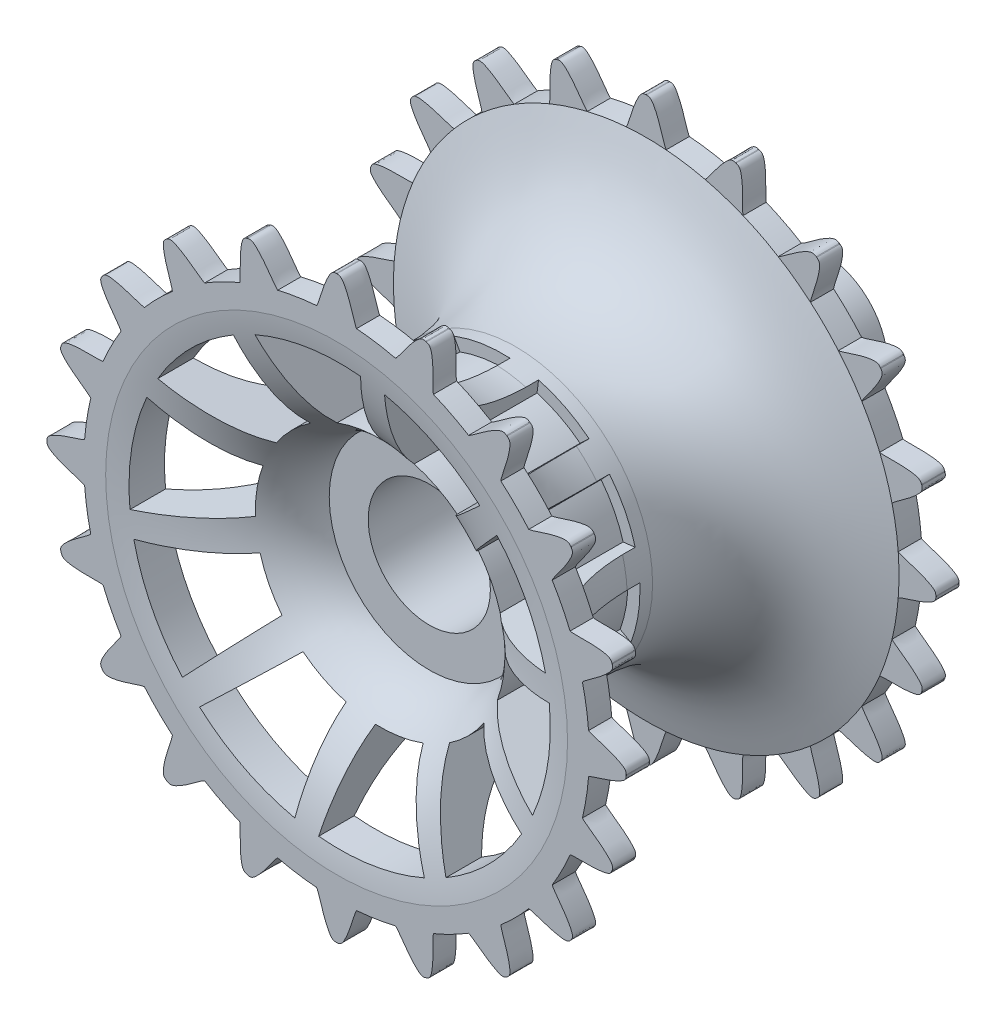
SolidWorks part; units mm, degrees
ref_plane "前视基准面" through (0, 0, 0) normal (0, 0, 1) x (1, 0, 0)
ref_plane "上视基准面" through (0, 0, 0) normal (0, 1, 0) x (1, 0, 0)
ref_plane "右视基准面" through (0, 0, 0) normal (1, 0, 0) x (0, 0, -1)
sketch "草图1" plane through (0, 0, 0) normal (0, 0, 1) x (1, 0, 0)
  line L0 (0, 0) -> (0, 27.5)
  line L1 (0, 0) -> (4.0987, 27.1928)
  line L2 (0, 0) -> (8.1058, 26.2783)
  line L3 (0, 0) -> (11.9318, 24.7766)
  line L4 (0, 0) -> (15.4913, 22.7216)
  line L5 (0, 0) -> (18.7048, 20.1589)
  line L6 (0, 0) -> (21.5004, 17.146)
  line L7 (0, 0) -> (23.8157, 13.75)
  line L8 (0, 0) -> (25.599, 10.0469)
  line L9 (0, 0) -> (26.8105, 6.1193)
  line L10 (0, 0) -> (27.4231, 2.0551)
  line L11 (0, 0) -> (27.4231, -2.0551)
  line L12 (0, 0) -> (26.8105, -6.1193)
  line L13 (0, 0) -> (25.599, -10.0469)
  line L14 (0, 0) -> (23.8157, -13.75)
  line L15 (0, 0) -> (21.5004, -17.146)
  line L16 (0, 0) -> (18.7048, -20.1589)
  line L17 (0, 0) -> (15.4913, -22.7216)
  line L18 (0, 0) -> (11.9318, -24.7766)
  line L19 (0, 0) -> (8.1058, -26.2783)
  line L20 (0, 0) -> (4.0987, -27.1928)
  line L21 (0, 0) -> (0, -27.5)
  line L22 (0, 0) -> (-4.0987, -27.1928)
  line L23 (0, 0) -> (-8.1058, -26.2783)
  line L24 (0, 0) -> (-11.9318, -24.7766)
  line L25 (0, 0) -> (-15.4913, -22.7216)
  line L26 (0, 0) -> (-18.7048, -20.1589)
  line L27 (0, 0) -> (-21.5004, -17.146)
  line L28 (0, 0) -> (-23.8157, -13.75)
  line L29 (0, 0) -> (-25.599, -10.0469)
  line L30 (0, 0) -> (-26.8105, -6.1193)
  line L31 (0, 0) -> (-27.4231, -2.0551)
  line L32 (0, 0) -> (-27.4231, 2.0551)
  line L33 (0, 0) -> (-26.8105, 6.1193)
  line L34 (0, 0) -> (-25.599, 10.0469)
  line L35 (0, 0) -> (-23.8157, 13.75)
  line L36 (0, 0) -> (-21.5004, 17.146)
  line L37 (0, 0) -> (-18.7048, 20.1589)
  line L38 (-13.5197, 19.8297) -> (-15.4913, 22.7216)
  line L39 (0, 0) -> (-11.9318, 24.7766)
  line L40 (0, 0) -> (-8.1058, 26.2783)
  line L41 (0, 0) -> (-4.0987, 27.1928)
  circle A0 centre (0, 0) radius 27.5
  circle A1 centre (0, 0) radius 24
  arc A2 (-7.5899, 24.606) -> (3.8378, 25.4624) centre (0, 0) ccw
  arc A3 (0, 25.75) -> (-3.8378, 25.4624) centre (0, 0) ccw
  spline S0 degree 3 poles (0, 27.5) (0.1146, 27.5014) (0.3487, 27.4756) (0.6091, 27.1808) (0.8232, 26.7995) (1.0497, 26.2917) (1.3089, 25.6127) (1.5804, 24.8085) (1.748, 24.1915) (1.8927, 23.9253) knots 0 0 0 0 0.082079 0.155052 0.267882 0.395303 0.549244 0.784807 1 1 1 1
  spline S1 degree 3 poles (0, 27.5) (-0.1146, 27.5014) (-0.3487, 27.4756) (-0.6091, 27.1808) (-0.8232, 26.7995) (-1.0497, 26.2917) (-1.3089, 25.6127) (-1.5804, 24.8085) (-1.748, 24.1915) (-1.8927, 23.9253) knots 0 0 0 0 0.082079 0.155052 0.267882 0.395303 0.549244 0.784807 1 1 1 1
  point P7 (-14.5055, 21.2756)
  point P48 (0, 0)
  dimension "D1" = 42
extrude "凸台-拉伸1" add sketch "草图1" along normal blind 31.6 contours S0 A0 L0 A1 | A3 S1 A1 L0 | A0 S1 A3 L0 region at (-0.476, 26.4646, 0) region at (0.6795, 25.3953, 0) region at (-0.7923, 24.8026, 0)
sketch "草图2" plane through (0, 0, 31.6) normal (0, 0, 1) x (1, 0, 0)
  circle A0 centre (0, 0) radius 24
extrude "凸台-拉伸2" add sketch "草图2" against normal blind 31.6
ref_axis "基准轴1" through (0, 0, 0) along (0, 0, 1)
pattern_circular "阵列(圆周)1" count 20 over 360 about axis through (0, 0, 0) along (0, 0, 1) of "凸台-拉伸1"
ref_plane "基准面1" through (0, 0, 29.4) normal (0, 0, 1) x (1, 0, 0)
ref_plane "基准面2" through (0, 0, 2.2) normal (0, 0, -1) x (-1, 0, 0)
sketch "草图3" plane through (0, 0, 29.4) normal (0, 0, 1) x (1, 0, 0)
  circle A0 centre (0, 0) radius 24
  circle A1 centre (0, 0) radius 39.1983
extrude "切除-拉伸1" cut sketch "草图3" against normal up to surface (27.2 mm away) up to plane "基准面2"
sketch "草图4" plane through (0, 0, 0) normal (1, 0, 0) x (0, 0, -1)
  line L0 (-2.2, 24) -> (-29.4, 24) construction
  line L1 (-2.2, 24) -> (-29.4, 24)
  line L2 (-29.4, -24) -> (-2.2, -24) construction
  line L3 (-29.4, -24) -> (-2.2, -24)
  line L4 (-15.8, -24) -> (-15.8, 24)
  line L5 (-46.2378, 0) -> (16.3604, 0)
  line L6 (-46.2378, -13) -> (16.3604, -13)
  line L7 (-46.2378, 13) -> (16.3604, 13)
  spline S0 degree 3 poles (-29.4, 24) (-28.6064, 21.6025) (-27.2686, 17.3198) (-21.841, 13.3668) (-17.9343, 12.9408) (-15.8, 13) knots 0 0 0 0 0.401325 0.665617 1 1 1 1
  spline S1 degree 3 poles (-2.2, 24) (-2.9936, 21.6025) (-4.3314, 17.3198) (-9.759, 13.3668) (-13.6657, 12.9408) (-15.8, 13) knots 0 0 0 0 0.401325 0.665617 1 1 1 1
revolve "切除-旋转1" cut sketch "草图4" angle 360 about L5 region at (0, 19.2493, 10.1874) region at (0, 19.2493, 21.4126)
sketch "草图5" plane through (0, 0, 0) normal (1, 0, 0) x (0, 0, -1)
  line L0 (-31.6, 12.5317) -> (-31.6, 9.1934) construction
  line L1 (-17.0021, 13) -> (-17.0021, -13) construction
  line L2 (-31.6, 0) -> (-31.6, 9.5)
  line L3 (-17.0021, 13) -> (-17.0021, -13)
  line L4 (-14.5979, 13) -> (-14.5979, -13) construction
  line L5 (-14.5979, 13) -> (-14.5979, -13)
  line L6 (-17.0021, 13) -> (-14.5979, 13)
  line L7 (-15.8, 13) -> (-15.8, 0)
  line L8 (-15.8, 0) -> (-15.8, 9.5)
  line L9 (-15.8, 9.5) -> (-22.8, 9.5)
  line L10 (-22.8, 9.5) -> (-22.8, 0)
  line L11 (-22.8, 0) -> (-31.6, 0)
  line L12 (-31.6, 27.5) -> (-31.6, 23.9253) construction
  line L13 (-31.6, 27.5) -> (-31.6, 23.9253)
  line L14 (-31.6, 21.9281) -> (-31.6, 0)
  spline S1 degree 3 poles (-31.6, 21.9281) (-31.059, 16.9429) (-28.6782, 10.2775) (-22.8, 9.5) knots 0 0 0 0 1 1 1 1
revolve "切除-旋转2" cut sketch "草图5" angle 360 about axis through (0, 0, 0) along (0, 0, 1) region at (0, 6.7239, 27.7812)
ref_plane "基准面3" through (0, 0, 15.8) normal (0, 0, 1) x (1, 0, 0)
mirror "镜向1" about plane through (0, 0, 15.8) normal (0, 0, 1) of "切除-旋转2"
sketch "草图6" plane through (0, 0, 31.6) normal (0, 0, 1) x (1, 0, 0)
  line L0 (3.7544, 23.7045) -> (0, 0)
  line L1 (16.9706, 16.9706) -> (0, 0)
  line L2 (23.7045, 3.7544) -> (0, 0)
  line L3 (21.3842, -10.8958) -> (0, 0)
  line L4 (10.8958, -21.3842) -> (0, 0)
  line L5 (-3.7544, -23.7045) -> (0, 0)
  line L6 (-16.9706, -16.9706) -> (0, 0)
  line L7 (-23.7045, -3.7544) -> (0, 0)
  line L8 (-21.3842, 10.8958) -> (0, 0)
  line L9 (-10.8958, 21.3842) -> (0, 0)
  line L10 (3.2323, 11.4007) -> (4.2584, 19.5414)
  line L11 (7.3234, 9.3161) -> (13.3063, 14.9313)
  line L12 (0.4489, 11.8415) -> (1.9886, 19.9009)
  line L13 (9.3161, 7.3234) -> (14.9313, 13.3063)
  line L14 (11.4007, 3.2323) -> (19.5414, 4.2584)
  line L15 (11.8415, 0.4489) -> (19.9009, 1.9886)
  line L16 (11.1232, -4.0862) -> (18.3124, -8.041)
  line L17 (9.8438, -6.5971) -> (17.269, -10.0886)
  line L18 (6.5971, -9.8438) -> (10.0886, -17.269)
  line L19 (4.0862, -11.1232) -> (8.041, -18.3124)
  line L20 (-0.4489, -11.8415) -> (-1.9886, -19.9009)
  line L21 (-3.2323, -11.4007) -> (-4.2584, -19.5414)
  line L22 (-7.3234, -9.3161) -> (-13.3063, -14.9313)
  line L23 (-9.3161, -7.3234) -> (-14.9313, -13.3063)
  line L24 (-11.4007, -3.2323) -> (-19.5414, -4.2584)
  line L25 (-11.8415, -0.4489) -> (-19.9009, -1.9886)
  line L26 (-11.1232, 4.0862) -> (-18.3124, 8.041)
  line L27 (-9.8438, 6.5971) -> (-17.269, 10.0886)
  line L28 (-6.5971, 9.8438) -> (-10.0886, 17.269)
  line L29 (-4.0862, 11.1232) -> (-8.041, 18.3124)
  arc A0 (5.5932, 23.3391) -> (1.8927, 23.9253) centre (0, 0) ccw construction
  circle A1 centre (0, 0) radius 11.85
  circle A2 centre (0, 0) radius 20
  point P17 (0, 0)
  point P60 (0, 0)
  dimension "D2" = 10
  dimension "D1" = 10
extrude "切除-拉伸2" cut sketch "草图6" against normal up to surface (15.8 mm away) contours L12 A2 L29 A1 | L11 A2 L10 A1 | L14 A2 L13 A1 | L16 A2 L15 A1 | L18 A2 L17 A1 | L20 A2 L19 A1 | L22 A2 L21 A1 | L24 A2 L23 A1 | L26 A2 L25 A1 | L28 A2 L27 A1 region at (7.3935, 14.5105, 31.6) region at (-2.5476, 16.085, 31.6) region at (14.5105, 7.3935, 31.6) region at (16.085, -2.5476, 31.6) region at (11.5156, -11.5156, 31.6) region at (2.5476, -16.085, 31.6) region at (-7.3935, -14.5105, 31.6) region at (-14.5105, -7.3935, 31.6) region at (-16.085, 2.5476, 31.6) region at (-11.5156, 11.5156, 31.6) up to plane "基准面3"
sketch "草图7" plane through (0, 0, 22.8) normal (0, 0, 1) x (1, 0, 0)
  circle A0 centre (0, 0) radius 5.8
extrude "切除-拉伸3" cut sketch "草图7" against normal blind 13.5
sketch "草图8" plane through (0, 0, 9.3) normal (0, 0, 1) x (1, 0, 0)
  circle A0 centre (0, 0) radius 1.65
extrude "切除-拉伸4" cut sketch "草图8" against normal through all
sketch "草图9" plane through (0, 0, 8.8) normal (0, 0, -1) x (-1, 0, 0)
  circle A0 centre (0, 0) radius 1.65
  circle A1 centre (0, 0) radius 6.25
  dimension "D1" = 12.5
extrude "凸台-拉伸3" add sketch "草图9" along normal blind 8.5
sketch "草图10" plane through (0, 0, 0.3) normal (0, 0, -1) x (-1, 0, 0)
  circle A0 centre (0, 0) radius 6
  circle A1 centre (0, 0) radius 2.5
  dimension "D1" = 12
  dimension "D2" = 5
extrude "凸台-拉伸4" add sketch "草图10" along normal blind 15
sketch "草图11" plane through (0, 0, 15.8) normal (0, 0, 1) x (1, 0, 0)
  circle A0 centre (0, 0) radius 25.65
  point P1 (-25.65, -1.218)
